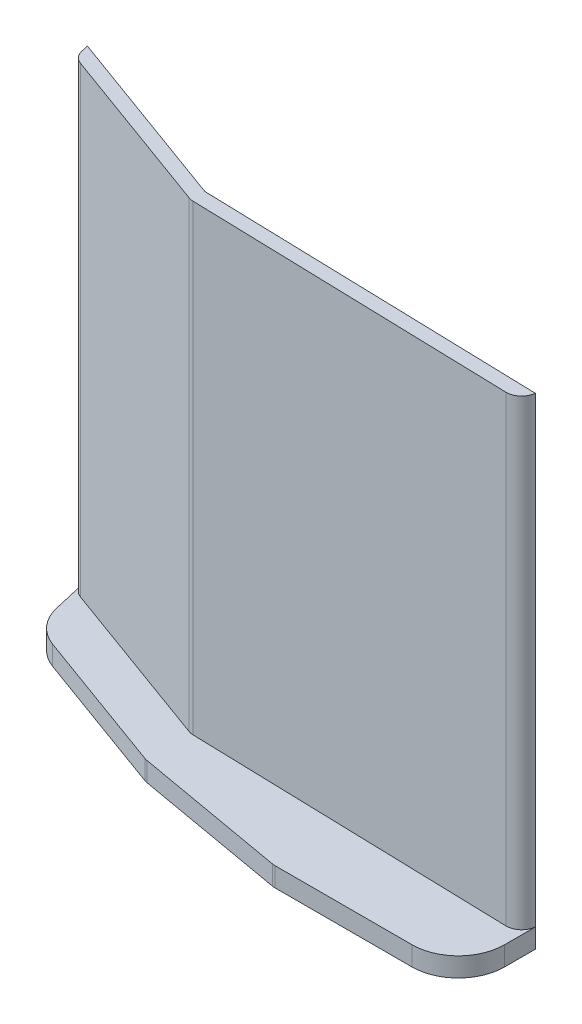
SolidWorks part; units mm, degrees
material "PET"
ref_plane "Front Plane" through (0, 0, 0) normal (0, 0, 1) x (1, 0, 0)
ref_plane "Top Plane" through (0, 0, 0) normal (0, 1, 0) x (1, 0, 0)
ref_plane "Right Plane" through (0, 0, 0) normal (1, 0, 0) x (0, 0, -1)
sketch "Sketch1" plane through (0, 0, 0) normal (0, 1, 0) x (1, 0, 0)
  line L0 (0, 0) -> (0, -12.7)
  line L1 (0, -12.7) -> (-30.4634, -12.7)
  line L2 (-30.4634, -12.7) -> (-56.0424, -8.1897)
  line L3 (-56.0424, -8.1897) -> (-84.038, 1.9998)
  line L4 (-84.038, 1.9998) -> (-86.5029, 12.6543)
  line L5 (-86.5029, 12.6543) -> (-56.0424, 1.5676)
  line L6 (-56.0424, 1.5676) -> (0, 0)
  point P3 (0, 0)
  point P9 (-56.0424, 1.5676)
  point P10 (0, 0)
  point P11 (0, 0)
  point P12 (-79.93, 7.0927)
  point P13 (-56.5502, 6.1421)
  point P14 (0, 0)
  point P15 (-57.1096, 5.5913)
  point P16 (-57.6565, 3.8282)
  point P17 (-34.4338, 0)
  point P18 (0, 0)
  point P19 (-30.4634, 0)
  point P20 (0, 0)
  point P21 (-0.4643, 0)
  dimension "D1" = 30.4634
  dimension "D2" = 12.7
  dimension "D3" = 56.0424
  dimension "D4" = 86.5029
  dimension "D5" = 170
  dimension "D6" = 170
  dimension "D7" = 84.038
  dimension "D8" = 1.5676
extrude "Gage Plate-side Extrude" add sketch "Sketch1" along normal blind 3.175
sketch "Sketch2" plane through (0, 3.175, 0) normal (0, 1, 0) x (1, 0, 0)
  line L12 (0, 0) -> (0, -2.3443)
  line L13 (0, -12.7) -> (0, 0) construction
  line L14 (0, -2.3443) -> (-56.0424, -0.7767)
  line L15 (-56.0424, -0.7767) -> (-85.9107, 10.0945)
  line L16 (-86.5029, 12.6543) -> (-84.038, 1.9998) construction
  line L17 (-85.9107, 10.0945) -> (-86.5029, 12.6543)
  line L18 (-86.5029, 12.6543) -> (-56.0424, 1.5676)
  line L19 (-56.0424, 1.5676) -> (0, 0)
  point P5 (0, 0)
  dimension "D1" = 0.5922
extrude "Boss-Extrude2" add sketch "Sketch2" along normal blind 76.2
fillet "Fillet1" radius 2.54 5 edges at (-30.4634, 1.5875, 12.7) (-56.0424, 1.5875, 8.1897) (-56.0424, 41.275, 0.7767) (0, 41.275, 2.3443) (-85.9107, 41.275, -10.0945)
fillet "Fillet2" radius 7.62 2 edges at (-84.038, 1.5875, -1.9998) (0, 1.5875, 12.7)
